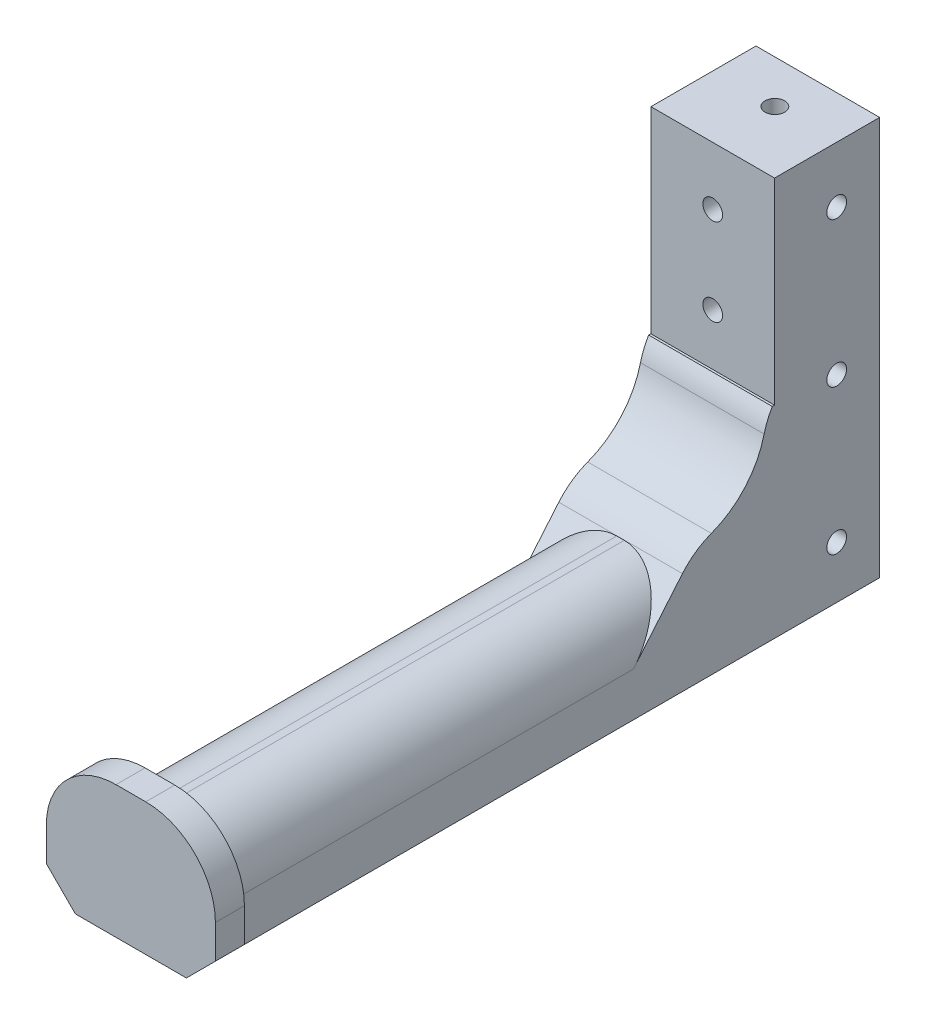
SolidWorks part; units mm, degrees
material "ABS"
ref_plane "Front" through (0, 0, 0) normal (0, 0, 1) x (1, 0, 0)
ref_plane "Top" through (0, 0, 0) normal (0, 1, 0) x (1, 0, 0)
ref_plane "Right" through (0, 0, 0) normal (1, 0, 0) x (0, 0, -1)
sketch "Sketch1" plane through (0, 0, 0) normal (0, 0, 1) x (1, 0, 0)
  line L1 (-10.65, -35) -> (10.65, -35)
  line L2 (-10.65, -35) -> (-10.65, 35)
  line L3 (-10.65, 35) -> (10.65, 35)
  line L4 (10.65, -35) -> (10.65, 35)
  line L5 (-10.65, -35) -> (10.65, 35) construction
  line L6 (-10.65, 35) -> (10.65, -35) construction
  point P0 (0, 0)
extrude "Boss-Extrude1" add sketch "Sketch1" against normal blind 3
sketch "Sketch2" plane through (0, 0, -3) normal (0, 0, -1) x (-1, 0, 0)
  line L0 (10.65, -35) -> (-10.65, -35) construction
  line L1 (-10.65, 35) -> (-7.7, 35)
  line L2 (-10.65, 35) -> (-10.65, -35)
  line L3 (-10.65, -35) -> (-7.7, -35)
  line L4 (-7.7, 35) -> (-7.7, -35)
  line L6 (10.65, 35) -> (7.7, 35)
  line L7 (10.65, 35) -> (10.65, -35)
  line L8 (10.65, -35) -> (7.7, -35)
  line L9 (7.7, 35) -> (7.7, -35)
  dimension "D1" = 15.4
extrude "Boss-Extrude2" add sketch "Sketch2" along normal blind 15.1
sketch "Sketch3" plane through (0, 0, -3) normal (0, 0, -1) x (-1, 0, 0)
  line L0 (7.7, 35) -> (7.7, -35) construction
  line L1 (-7.7, 35) -> (7.7, 35)
  line L2 (-7.7, 35) -> (-7.7, 32)
  line L3 (-7.7, 32) -> (7.7, 32)
  line L4 (7.7, 35) -> (7.7, 32)
extrude "Boss-Extrude3" add sketch "Sketch3" along normal up to surface (15.1 mm away) up to face at (9.175, 0, -18.1)
sketch "Sketch4" plane through (0, 0, 0) normal (0, 0, 1) x (1, 0, 0)
  line L1 (-10.65, -16.0991) -> (10.65, -16.0991)
  line L2 (-10.65, -16.0991) -> (-10.65, -35)
  line L3 (-10.65, -35) -> (10.65, -35)
  line L4 (10.65, -16.0991) -> (10.65, -35)
  line L6 (-10.65, -35) -> (10.65, -35) construction
extrude "Boss-Extrude4" add sketch "Sketch4" along normal blind 95
sketch "Sketch6" plane through (0, 0, 95) normal (0, 0, 1) x (1, 0, 0)
  line L1 (-14.7909, -12.2147) -> (14.3271, -12.2147)
  line L2 (-14.7909, -12.2147) -> (-14.7909, -35)
  line L3 (-14.7909, -35) -> (14.3271, -35)
  line L4 (14.3271, -12.2147) -> (14.3271, -35)
  line L5 (-14.7909, -12.2147) -> (14.3271, -35) construction
  line L6 (-14.7909, -35) -> (14.3271, -12.2147) construction
  line L7 (-10.65, -35) -> (10.65, -35) construction
  point P0 (-0.2319, -23.6074)
extrude "Boss-Extrude5" add sketch "Sketch6" along normal blind 5
sketch "Sketch9" plane through (0, 0, 0) normal (0, 0, 1) x (1, 0, 0)
  line L0 (10.65, -16.0991) -> (10.65, 35) construction
  line L1 (-10.65, -16.0991) -> (10.65, -16.0991)
  line L2 (-10.65, -16.0991) -> (-10.65, 1.1229)
  line L3 (-10.65, 1.1229) -> (10.65, 1.1229)
  line L4 (10.65, -16.0991) -> (10.65, 1.1229)
extrude "Boss-Extrude6" add sketch "Sketch9" along normal blind 16
sketch "Sketch12" plane through (-10.65, 0, 0) normal (-1, 0, 0) x (0, 0, 1)
  circle A0 centre (16, 1.1229) radius 14.608
extrude "Cut-Extrude1" cut sketch "Sketch12" against normal through all
chamfer "Chamfer3" distance 3 angle 45 1 edges at (0, -13.4851, 16)
chamfer "Chamfer4" distance 1 angle 45 1 edges at (0, 1.1229, 1.392)
chamfer "Chamfer5" distance 5 angle 45 1 edges at (-14.7909, -35, 97.5)
chamfer "Chamfer6" distance 5 angle 45 1 edges at (14.3271, -35, 97.5)
fillet "Fillet4" radius 12 2 edges at (-14.7909, -12.2147, 97.5) (14.3271, -12.2147, 97.5)
fillet "Fillet5" radius 12 1 edges at (0, -13.2715, 13.5111)
fillet "Fillet6" radius 12 1 edges at (0, 0.0861, 1.4288)
fillet "Fillet7" radius 10 2 edges
hole_wizard "M3 Clearance Hole1" positions "Sketch14" profile "Sketch13" hole size "M3" standard "ANSI Metric" end condition through all
sketch "Sketch14" plane through (10.65, 0, 0) normal (1, 0, 0) x (0, 0, -1)
  line L1 (10.7, -24.6771) -> (10.7, 35) construction
  line L2 (18.1, 35) -> (0, 35) construction
  line L4 (-95, -33.6771) -> (18.1, -33.6771) construction
  line L5 (18.1, 35) -> (18.1, -33.6771) construction
  point P0 (10.7, 25.3229)
  point P2 (10.7, 0.3229)
  point P4 (10.7, -24.6771)
  dimension "D1" = 25
  dimension "D2" = 25
  dimension "D3" = 9
  dimension "D4" = 7.4
sketch "Sketch13" plane through (10.65, 25.3229, -10.7) normal (0, 1, 0) x (0, 0, -1)
  line L0 (0, 0) -> (0, 25.4409)
  line L1 (0, 25.4409) -> (1.7, 25.4409)
  line L2 (1.7, 25.4409) -> (1.7, 0)
  line L5 (1.7, 0) -> (0, 0)
  line L11 (0, -6.35) -> (0, 107.95) construction
  dimension "Thru Hole Dia." = 3.4
  dimension "Thru Hole Depth" = 25.4409
hole_wizard "M3 Clearance Hole2" positions "Sketch16" profile "Sketch15" hole size "M3" standard "ANSI Metric" end condition through all
sketch "Sketch16" plane through (0, 35, 0) normal (0, 1, 0) x (1, 0, 0)
  line L4 (0, 0) -> (0, 18.1) construction
  line L5 (10.65, 0) -> (-10.65, 0) construction
  line L6 (-10.65, 18.1) -> (10.65, 18.1) construction
  point P0 (0, 10.7)
  dimension "D1" = 7.4
sketch "Sketch15" plane through (0, 35, -10.7) normal (1, 0, 0) x (0, 0, 1)
  line L0 (0, 0) -> (0, 70.0001)
  line L1 (0, 70.0001) -> (1.7, 70.0001)
  line L2 (1.7, 70.0001) -> (1.7, 0)
  line L5 (1.7, 0) -> (0, 0)
  line L11 (0, -6.35) -> (0, 107.95) construction
  dimension "Thru Hole Dia." = 3.4
  dimension "Thru Hole Depth" = 70.0001
hole_wizard "M3 Clearance Hole3" positions "Sketch20" profile "Sketch19" hole size "M3" standard "ANSI Metric" end condition through all
sketch "Sketch20" plane through (0, 0, 0) normal (0, 0, 1) x (1, 0, 0)
  line L0 (0, 35) -> (0, 1.1229) construction
  line L1 (10.65, 35) -> (-10.65, 35) construction
  line L2 (10.65, 1.1229) -> (-10.65, 1.1229) construction
  point P0 (0, 10)
  point P2 (0, 25)
  dimension "D1" = 10
  dimension "D2" = 15
sketch "Sketch19" plane through (0, 10, 0) normal (1, 0, 0) x (0, -1, 0)
  line L0 (0, 0) -> (0, 18.1)
  line L1 (0, 18.1) -> (1.7, 18.1)
  line L2 (1.7, 18.1) -> (1.7, 0)
  line L5 (1.7, 0) -> (0, 0)
  line L11 (0, -6.35) -> (0, 107.95) construction
  dimension "Thru Hole Dia." = 3.4
  dimension "Thru Hole Depth" = 18.1
